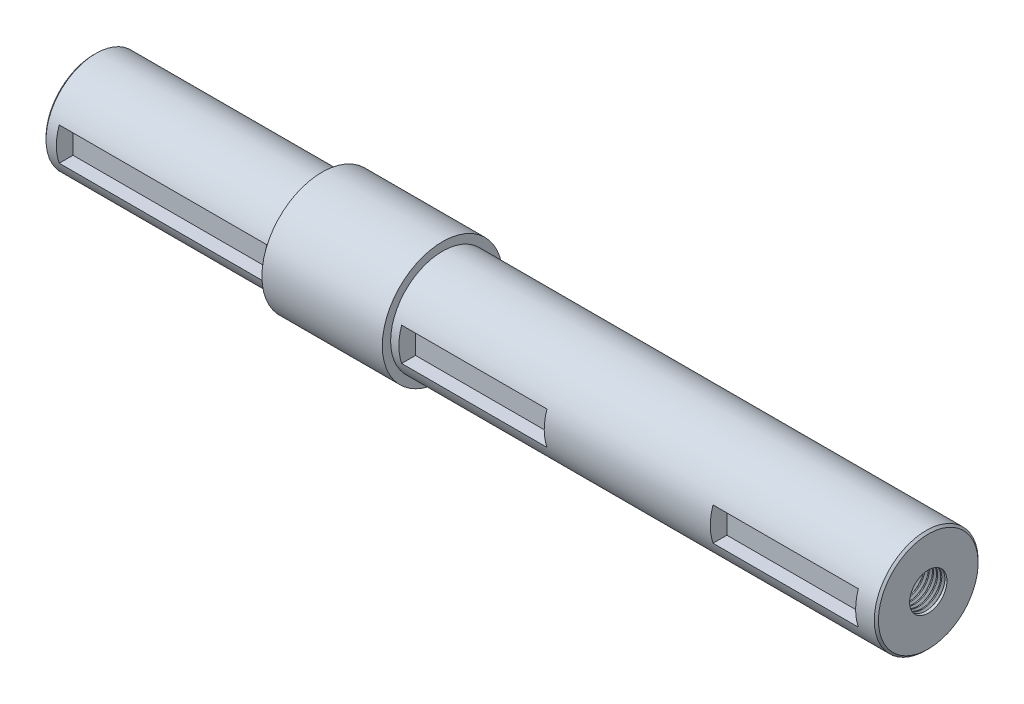
SolidWorks part; units mm, degrees
ref_plane "Piano frontale" through (0, 0, 0) normal (0, 0, 1) x (1, 0, 0)
ref_plane "Piano superiore" through (0, 0, 0) normal (0, 1, 0) x (1, 0, 0)
ref_plane "Piano destro" through (0, 0, 0) normal (1, 0, 0) x (0, 0, -1)
sketch "Schizzo2" plane through (0, 0, 0) normal (0, 0, 1) x (1, 0, 0)
  line L0 (-79.7949, 0) -> (79.1795, 0) construction
  line L1 (-58.0513, 0) -> (-58.0513, 12)
  line L2 (-58.0513, 12) -> (-3.0513, 12)
  line L3 (-3.0513, 12) -> (-3.0513, 14.5)
  line L4 (-3.0513, 14.5) -> (25.9487, 14.5)
  line L5 (25.9487, 14.5) -> (25.9487, 12.5)
  line L6 (25.9487, 12.5) -> (142.9487, 12.5)
  line L7 (142.9487, 12.5) -> (142.9487, 0)
  line L8 (142.9487, 0) -> (-58.0513, 0)
  dimension "D1" = 24
  dimension "D2" = 29
  dimension "D3" = 25
  dimension "D4" = 55
  dimension "D5" = 29
  dimension "D6" = 117
revolve "Rivoluzione1" add sketch "Schizzo2" angle 360 about L0
ref_plane "Piano1" through (0, 0, 12) normal (0, 0, 1) x (1, 0, 0)
sketch "Schizzo4" plane through (0, 0, 12) normal (0, 0, 1) x (1, 0, 0)
  line L0 (-65.3488, 0) -> (5.2462, 0) construction
  line L1 (-3.0513, 14.5) -> (-3.0513, -14.5) construction
  line L2 (-55.0513, 4) -> (-5.0513, 4)
  line L3 (-55.0513, 4) -> (-55.0513, -4)
  line L4 (-55.0513, -4) -> (-5.0513, -4)
  line L5 (-5.0513, 4) -> (-5.0513, -4)
  line L6 (-55.0513, 4) -> (-5.0513, -4) construction
  line L7 (-55.0513, -4) -> (-5.0513, 4) construction
  point P3 (-30.0513, 0)
  dimension "D1" = 50
  dimension "D2" = 2
  dimension "D3" = 8
extrude "Taglio-Estrusione1" cut sketch "Schizzo4" against normal blind 4
ref_plane "Piano2" through (0, 0, 12.5) normal (0, 0, 1) x (1, 0, 0)
sketch "Schizzo5" plane through (0, 0, 12.5) normal (0, 0, 1) x (1, 0, 0)
  line L0 (21.4829, 0) -> (166.3604, 0) construction
  line L1 (25.9487, -14.5) -> (25.9487, 14.5) construction
  line L2 (27.9487, 4) -> (62.9487, 4)
  line L3 (27.9487, 4) -> (27.9487, -4)
  line L4 (27.9487, -4) -> (62.9487, -4)
  line L5 (62.9487, 4) -> (62.9487, -4)
  line L6 (27.9487, 4) -> (62.9487, -4) construction
  line L7 (27.9487, -4) -> (62.9487, 4) construction
  line L8 (102.9487, 4) -> (137.9487, 4)
  line L9 (102.9487, 4) -> (102.9487, -4)
  line L10 (102.9487, -4) -> (137.9487, -4)
  line L11 (137.9487, 4) -> (137.9487, -4)
  line L12 (102.9487, 4) -> (137.9487, -4) construction
  line L13 (102.9487, -4) -> (137.9487, 4) construction
  point P3 (45.4487, 0)
  point P8 (120.4487, 0)
  dimension "D1" = 35
  dimension "D2" = 35
  dimension "D3" = 40
  dimension "D4" = 8
  dimension "D5" = 8
  dimension "D6" = 2
extrude "Taglio-Estrusione2" cut sketch "Schizzo5" against normal blind 4
chamfer "Smusso1" distance 0.5 angle 45 2 edges at (142.9487, 0, 12.5) (-58.0513, 0, 12)
hole_wizard "Foro per Vite M8-1" positions "Schizzo6" profile "Schizzo7" hole size "M8" standard "Ansi Metric"
sketch "Schizzo6" plane through (142.9487, 0, 0) normal (1, 0, 0) x (0, 0, -1)
  point P0 (0, 0)
sketch "Schizzo7" plane through (142.9487, 0, 0) normal (0, 1, 0) x (0, 0, -1)
  line L0 (0, 0) -> (0, 22.7039)
  line L1 (0, 22.7039) -> (4.5, 20)
  line L2 (4.5, 20) -> (4.5, 0)
  line L5 (4.5, 0) -> (0, 0)
  line L10 (0, 22.7039) -> (-4.5, 20) construction
  line L11 (0, -6.35) -> (0, 107.95) construction
  dimension "Hole Dia." = 9
  dimension "Hole Depth" = 20
  dimension "Drill Angle" = 118
hole_wizard "Foro per Vite M8-2" positions "Schizzo8" profile "Schizzo9" hole size "M8" standard "Ansi Metric"
sketch "Schizzo8" plane through (-58.0513, 0, 0) normal (-1, 0, 0) x (0, 0, 1)
  point P0 (0, 0)
sketch "Schizzo9" plane through (-58.0513, 0, 0) normal (0, 1, 0) x (0, 0, 1)
  line L0 (0, 0) -> (0, 22.7039)
  line L1 (0, 22.7039) -> (4.5, 20)
  line L2 (4.5, 20) -> (4.5, 0)
  line L5 (4.5, 0) -> (0, 0)
  line L10 (0, 22.7039) -> (-4.5, 20) construction
  line L11 (0, -6.35) -> (0, 107.95) construction
  dimension "Hole Dia." = 9
  dimension "Hole Depth" = 20
  dimension "Drill Angle" = 118
thread "Filettatura1" pitch 1 method cut profile "Profilo filettatura1" start angle 0, offset 0, length 15, pitch 1, diameter 9
ref_plane "Piano3" through (142.9487, 0, 4.5) normal (0, -1, 0) x (0, 0, 1)
sketch "Profilo filettatura1" plane through (142.9487, 0, 4.5) normal (0, -1, 0) x (0, 0, 1)
  line L0 (0, 0) -> (0, 1) construction
  line L1 (0, 0) -> (0.5413, 0.3125)
  line L2 (0.5413, 0.3125) -> (0.5413, 0.4375)
  line L3 (0.5413, 0.4375) -> (0, 0.75)
  line L4 (0.5413, 0.375) -> (0, 0.375) construction
  line L11 (0, 0) -> (0, 0.75)
  point P2 (0, 0)
  dimension "Pitch" = 1
  dimension "Profile_Angle" = 60
  dimension "Profile_Land" = 0.125
  dimension "Profile_Height" = 0.5413
thread "Filettatura2" pitch 1 method cut profile "Profilo filettatura2" start angle 0, offset 0, length 15, pitch 1, diameter 9
ref_plane "Piano4" through (-58.0513, 0, -4.5) normal (0, -1, 0) x (0, 0, -1)
sketch "Profilo filettatura2" plane through (-58.0513, 0, -4.5) normal (0, -1, 0) x (0, 0, -1)
  line L0 (0, 0) -> (0, 1) construction
  line L1 (0, 0) -> (0.5413, 0.3125)
  line L2 (0.5413, 0.3125) -> (0.5413, 0.4375)
  line L3 (0.5413, 0.4375) -> (0, 0.75)
  line L4 (0.5413, 0.375) -> (0, 0.375) construction
  line L11 (0, 0) -> (0, 0.75)
  point P2 (0, 0)
  dimension "Pitch" = 1
  dimension "Profile_Angle" = 60
  dimension "Profile_Land" = 0.125
  dimension "Profile_Height" = 0.5413
